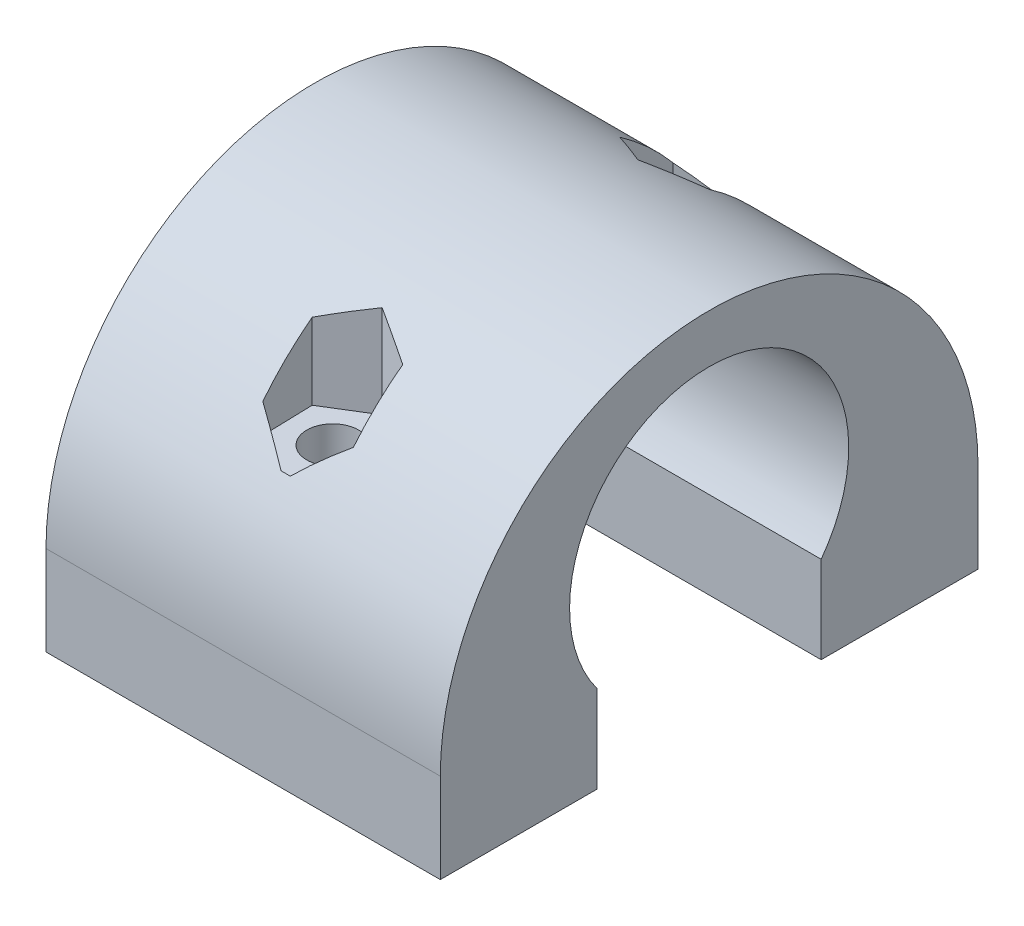
SolidWorks part; units mm, degrees
ref_plane "Front Plane" through (0, 0, 0) normal (0, 0, 1) x (1, 0, 0)
ref_plane "Top Plane" through (0, 0, 0) normal (0, 1, 0) x (1, 0, 0)
ref_plane "Right Plane" through (0, 0, 0) normal (1, 0, 0) x (0, 0, -1)
sketch "Sketch1" plane through (0, 0, 0) normal (0, 1, 0) x (1, 0, 0)
  line L1 (-21.0811, 11.7568) -> (0.9189, 11.7568)
  line L2 (-21.0811, 11.7568) -> (-21.0811, -18.2432)
  line L3 (-21.0811, -18.2432) -> (0.9189, -18.2432)
  line L4 (0.9189, 11.7568) -> (0.9189, -18.2432)
  dimension "D1" = 30
  dimension "D2" = 22
extrude "Boss-Extrude1" add sketch "Sketch1" along normal blind 20
fillet "Fillet2" 2 edges at (-10.0811, 20, -11.7568) (-10.0811, 20, 18.2432) type full round first side face at (-10.0811, 10, -11.7568) second side face at (-10.0811, 10, 18.2432) middle face at (-10.0811, 20, 3.2432)
sketch "Sketch7" plane through (0, 0, 0) normal (0, -1, 0) x (1, 0, 0)
  line L1 (-21.0811, -11.7568) -> (0.9189, -11.7568)
  line L2 (-21.0811, -11.7568) -> (-21.0811, -3.4568)
  line L3 (-21.0811, -3.4568) -> (0.9189, -3.4568)
  line L4 (0.9189, -11.7568) -> (0.9189, -3.4568)
  line L8 (-21.0811, 9.9432) -> (0.9189, 9.9432)
  line L9 (-21.0811, 9.9432) -> (-21.0811, 18.2432)
  line L10 (-21.0811, 18.2432) -> (0.9189, 18.2432)
  line L11 (0.9189, 9.9432) -> (0.9189, 18.2432)
  line L15 (-21.0811, -11.7568) -> (-21.0811, 18.2432) construction
  line L16 (0.9189, 18.2432) -> (0.9189, -11.7568) construction
  dimension "D1" = 8.3
  dimension "D2" = 8.3
extrude "Boss-Extrude2" add sketch "Sketch7" against normal blind 3.988
sketch "Sketch4" plane through (0, 0, 0) normal (0, -1, 0) x (-1, 0, 0)
  line L1 (-0.9189, -18.2432) -> (-0.9189, 11.7568) construction
  line L3 (-0.9189, -18.2432) -> (-0.9189, 11.7568) construction
  line L6 (21.0811, -18.2432) -> (-0.9189, -18.2432) construction
  circle A0 centre (10.0811, 6.7568) radius 1.45
  circle A1 centre (10.0811, -13.2432) radius 1.45
  dimension "D1" = 20
  dimension "D3" = 5
  dimension "D2" = 11
  dimension "D6" = 11
sketch "Sketch3" plane through (-21.0811, 0, 0) normal (-1, 0, 0) x (0, 0, 1)
  line L2 (18.2432, 5) -> (18.2432, 0) construction
  circle A0 centre (3.2432, 9.5) radius 7.7866
  arc A1 (18.2432, 5) -> (-11.7568, 5) centre (3.2432, 5) ccw construction
  dimension "D2" = 4.5
  dimension "D1" = 15
extrude "Cut-Extrude2" cut sketch "Sketch3" against normal blind 25
extrude "Cut-Extrude3" cut sketch "Sketch4" against normal blind 19
sketch "Sketch9" plane through (0, 0, 0) normal (0, -1, 0) x (1, 0, 0)
  line L1 (-21.0811, -3.0068) -> (0.9189, -3.0068)
  line L2 (-21.0811, -3.0068) -> (-21.0811, 9.4932)
  line L3 (-21.0811, 9.4932) -> (0.9189, 9.4932)
  line L4 (0.9189, -3.0068) -> (0.9189, 9.4932)
  line L5 (0.9189, -11.7568) -> (-21.0811, -11.7568) construction
  line L7 (-21.0811, -11.7568) -> (-21.0811, 18.2432) construction
  dimension "D1" = 12.5
  dimension "D2" = 8.75
  dimension "D3" = 22
extrude "Cut-Extrude5" cut sketch "Sketch9" against normal blind 5
ref_plane "Plane1" through (0, 15, 0) normal (0, -1, 0) x (-1, 0, 0)
sketch "Sketch11" plane through (0, 15, 0) normal (0, -1, 0) x (-1, 0, 0)
  line L1 (7.5847, -14.5914) -> (10.0004, -16.0792)
  line L2 (10.0004, -16.0792) -> (12.4968, -14.7311)
  line L3 (12.4968, -14.7311) -> (12.5775, -11.8951)
  line L4 (12.5775, -11.8951) -> (10.1617, -10.4073)
  line L5 (10.1617, -10.4073) -> (7.6654, -11.7554)
  line L6 (7.6654, -11.7554) -> (7.5847, -14.5914)
  line L7 (7.5629, 5.2456) -> (10.1306, 3.8204)
  line L8 (10.1306, 3.8204) -> (12.6488, 5.3315)
  line L9 (12.6488, 5.3315) -> (12.5993, 8.2679)
  line L10 (12.5993, 8.2679) -> (10.0315, 9.6931)
  line L11 (10.0315, 9.6931) -> (7.5133, 8.182)
  line L12 (7.5133, 8.182) -> (7.5629, 5.2456)
  circle A0 centre (10.0811, -13.2432) radius 2.457 construction
  circle A1 centre (10.0811, 6.7568) radius 2.5434 construction
extrude "Cut-Extrude6" cut sketch "Sketch11" against normal blind 5 and the other way blind 2
